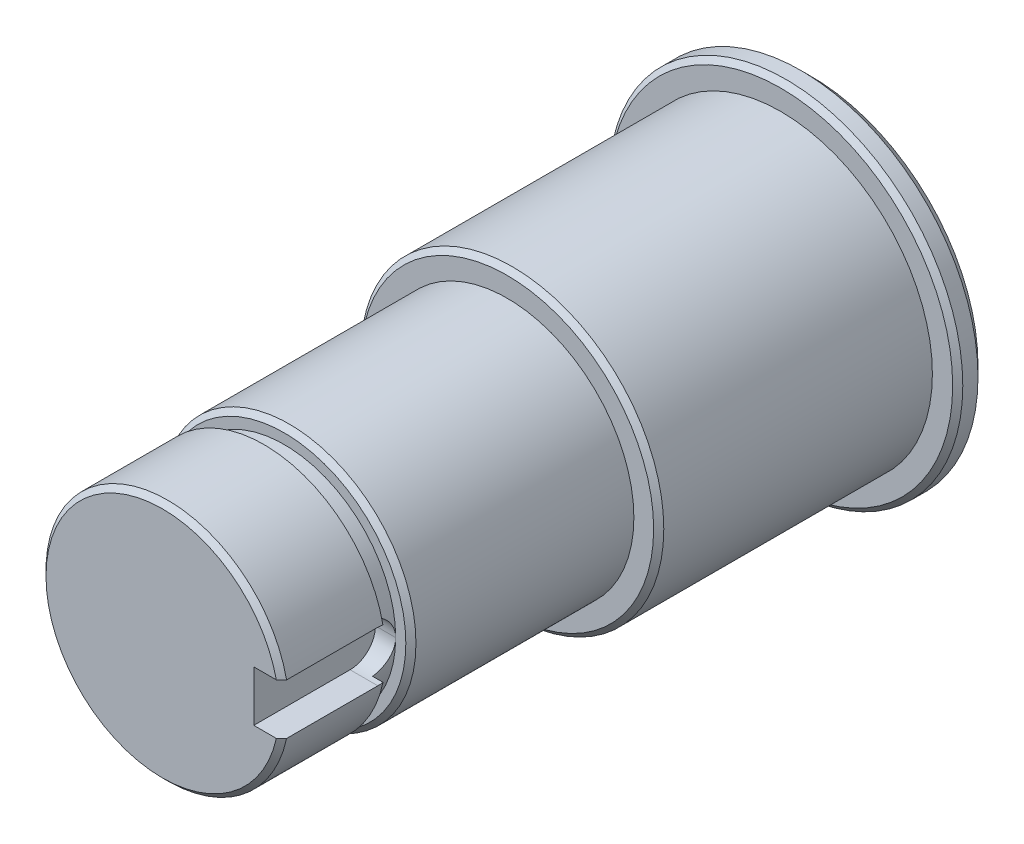
SolidWorks part; units mm, degrees
ref_plane "前视基准面" through (0, 0, 0) normal (0, 0, 1) x (1, 0, 0)
ref_plane "上视基准面" through (0, 0, 0) normal (0, 1, 0) x (1, 0, 0)
ref_plane "右视基准面" through (0, 0, 0) normal (1, 0, 0) x (0, 0, -1)
sketch "草图1" plane through (0, 0, 0) normal (0, 0, 1) x (1, 0, 0)
  circle A0 centre (0, 0) radius 17.45
extrude "拉伸1" add sketch "草图1" along normal blind 3
sketch "草图2" plane through (0, 0, 3) normal (0, 0, 1) x (1, 0, 0)
  circle A0 centre (0, 0) radius 14.95
extrude "拉伸2" add sketch "草图2" along normal blind 27
sketch "草图4" plane through (0, 0, 30) normal (0, 0, 1) x (1, 0, 0)
  circle A0 centre (0, 0) radius 12.5
extrude "拉伸3" add sketch "草图4" along normal blind 22
sketch "草图5" plane through (0, 0, 52) normal (0, 0, 1) x (1, 0, 0)
  circle A0 centre (0, 0) radius 12
extrude "拉伸4" add sketch "草图5" along normal blind 12
chamfer "倒角1" distance 0.5 angle 45 1 edges at (12, 0, 64)
sketch "草图6" plane through (0, 0, 0) normal (0, 1, 0) x (1, 0, 0)
  line L1 (-12, -52) -> (-11, -52)
  line L2 (-12, -52) -> (-12, -54)
  line L3 (-12, -54) -> (-11, -54)
  line L4 (-11, -52) -> (-11, -54)
  dimension "D1" = 1
  dimension "D2" = 2
ref_axis "基准轴1" through (0, 0, 52) along (0, 0, -1)
revolve "切除-旋转1" cut sketch "草图6" angle 360 about axis through (0, 0, 52) along (0, 0, -1)
chamfer "倒角2" distance 0.5 angle 45 3 edges at (17.45, 0, 3) (14.95, 0, 30) (12.5, 0, 52)
chamfer "倒角3" distance 1 angle 45 1 edges at (17.45, 0, 0)
ref_plane "基准面1" through (12, 0, 0) normal (1, 0, 0) x (0, 0, -1)
sketch "草图7" plane through (12, 0, 0) normal (1, 0, 0) x (0, 0, -1)
  line L0 (-64, 11.5) -> (-64, -11.5) construction
  line L1 (-64, 2.5) -> (-52, 2.5)
  line L2 (-64, 2.5) -> (-64, -2.5)
  line L3 (-64, -2.5) -> (-52, -2.5)
  line L4 (-52, 2.5) -> (-52, -2.5)
  line L5 (-52, 11) -> (-52, -11) construction
extrude "切除-拉伸1" cut sketch "草图7" against normal blind 3
fillet "圆角1" radius 2.5 2 edges at (9.8561, -2.5, 52) (9.8561, 2.5, 52)
